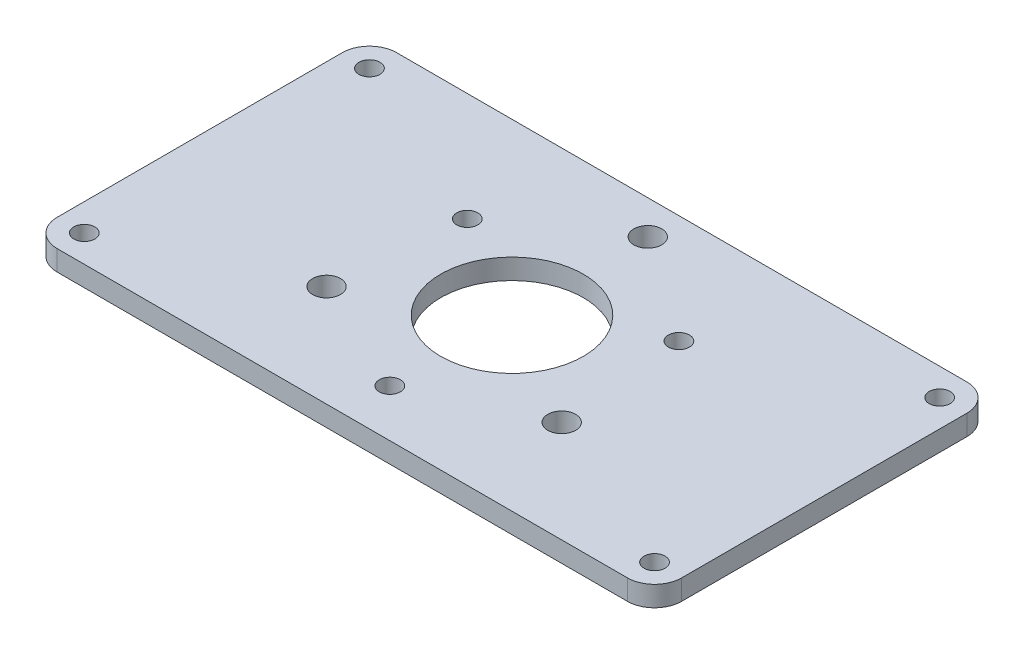
SolidWorks part; units mm, degrees
material "Thornel Mat VMA"
ref_plane "Front Plane" through (0, 0, 0) normal (0, 0, 1) x (1, 0, 0)
ref_plane "Top Plane" through (0, 0, 0) normal (0, 1, 0) x (1, 0, 0)
ref_plane "Right Plane" through (0, 0, 0) normal (1, 0, 0) x (0, 0, -1)
sketch "Sketch1" plane through (0, 0, 0) normal (0, 1, 0) x (1, 0, 0)
  line L0 (0, 0) -> (0, 79.06) construction
  line L1 (-46, -25) -> (46, -25)
  line L2 (-46, -25) -> (-46, 25)
  line L3 (-46, 25) -> (46, 25)
  line L4 (46, -25) -> (46, 25)
  line L5 (-46, -25) -> (46, 25) construction
  line L6 (-46, 25) -> (46, -25) construction
  line L7 (0, 0) -> (104.6127, 0) construction
  circle A0 centre (0, 0) radius 10.5
  circle A1 centre (42, 21) radius 1.55
  circle A2 centre (-42, 21) radius 1.55
  circle A3 centre (42, -21) radius 1.55
  circle A4 centre (-42, -21) radius 1.55
  circle A5 centre (0, 20) radius 2.05
  circle A6 centre (0, -18) radius 1.55
  circle A7 centre (-15.5885, 9) radius 1.55
  circle A8 centre (17.3205, -10) radius 2.05
  circle A9 centre (15.5885, 9) radius 1.55
  circle A10 centre (-17.3205, -10) radius 2.05
  point P0 (0, 0)
  point P33 (0, 0)
  dimension "D3" = 3.1
  dimension "D4" = 4
  dimension "D5" = 4
  dimension "D6" = 21
  dimension "D7" = 4.1
  dimension "D8" = 20
  dimension "D9" = 18
  dimension "D1" = 50
  dimension "D2" = 92
  dimension "D10" = 3
extrude "Boss-Extrude1" add sketch "Sketch1" along normal blind 3
fillet "Fillet1" radius 4 4 edges at (46, 1.5, -25) (46, 1.5, 25) (-46, 1.5, 25) (-46, 1.5, -25)
